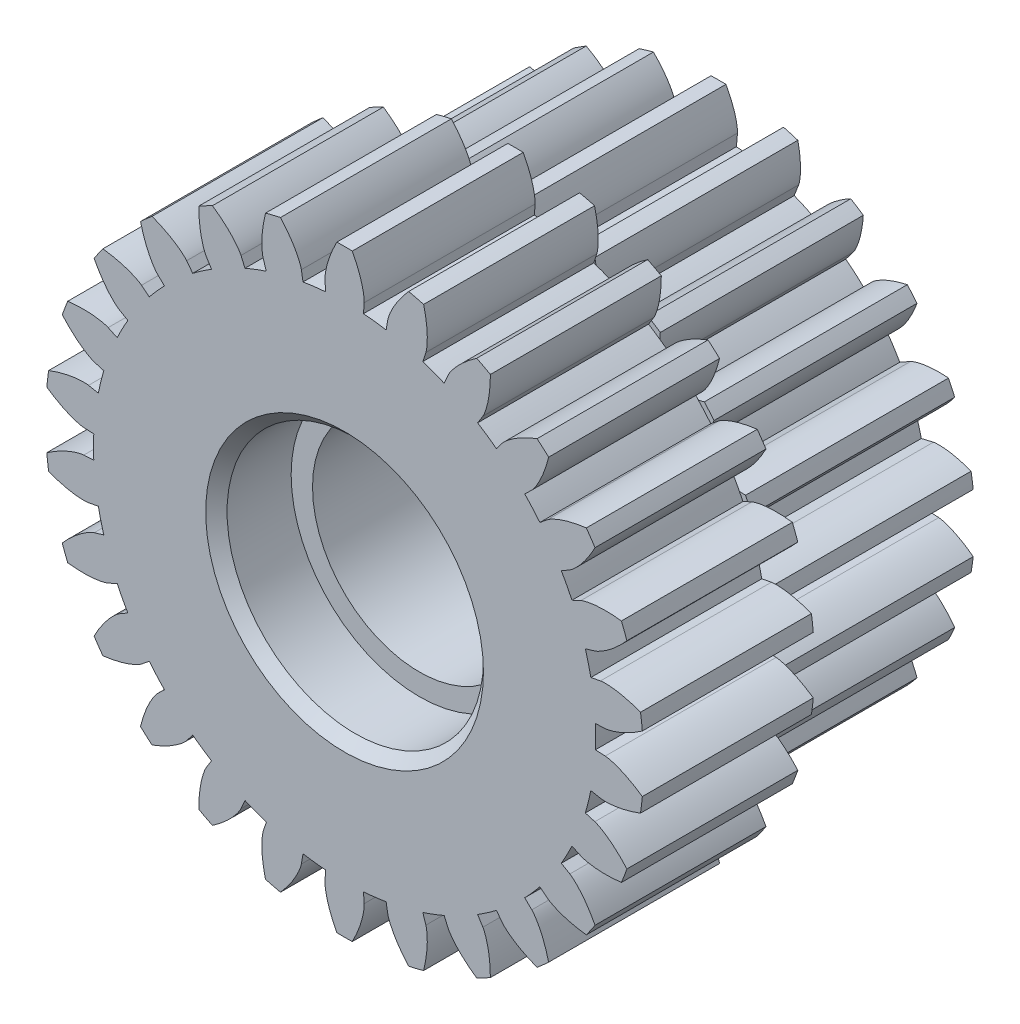
SolidWorks part; units mm, degrees
ref_plane "Front Plane" through (0, 0, 0) normal (0, 0, 1) x (1, 0, 0)
ref_plane "Top Plane" through (0, 0, 0) normal (0, 1, 0) x (1, 0, 0)
ref_plane "Right Plane" through (0, 0, 0) normal (1, 0, 0) x (0, 0, -1)
sketch "Sketch1" plane through (0, 0, 0) normal (0, 0, 1) x (1, 0, 0)
  circle A0 centre (0, 0) radius 14
  dimension "D1" = 28
extrude "Boss-Extrude1" add sketch "Sketch1" along normal mid plane 8
sketch "Sketch2" plane through (0, 0, 0) normal (0, 0, 1) x (1, 0, 0)
  line L0 (0, 0) -> (12.9865, 0.5914) construction
  line L1 (0, 0) -> (13, 0) construction
  line L2 (0, 0) -> (12.9865, -0.5914) construction
  line L3 (12.2009, -0.5557) -> (11.7378, -0.5346)
  line L4 (12.2034, 0.5558) -> (11.7378, 0.5346)
  circle A0 centre (0, 0) radius 13 construction
  circle A1 centre (0, 0) radius 12.216 construction
  circle A2 centre (0, 0) radius 11.75
  circle A3 centre (0, 0) radius 14 construction
  circle A4 centre (0, 0) radius 14
  spline S0 degree 4 poles (12.2034, 0.5558) (12.2075, 0.556) (12.2192, 0.5569) (12.2412, 0.5593) (12.2771, 0.5643) (12.3226, 0.5721) (12.3813, 0.5841) (12.45, 0.6003) (12.5252, 0.6205) (12.6066, 0.645) (12.6873, 0.6717) (12.7674, 0.7004) (12.8467, 0.7308) (12.9423, 0.7698) (13.0562, 0.8195) (13.1881, 0.882) (13.3363, 0.9581) (13.4855, 1.041) (13.631, 1.127) (13.7761, 1.219) (13.9153, 1.3115) (14.0579, 1.4127) (14.1886, 1.5087) (14.3326, 1.6219) (14.4482, 1.7148) (14.598, 1.8432) (14.6858, 1.9208) (14.7875, 2.0136) (14.8322, 2.0559) (14.8598, 2.0818) knots 0 0 0 0 0 0.005377 0.015084 0.028532 0.04661 0.064855 0.092111 0.119476 0.146842 0.174209 0.201575 0.228941 0.256307 0.307035 0.361767 0.4165 0.471232 0.525964 0.580697 0.635429 0.690161 0.744894 0.799626 0.854358 0.909091 0.954545 1 1 1 1 1 construction
  spline S1 degree 4 poles (12.2034, 0.5558) (12.2075, 0.556) (12.2192, 0.5569) (12.2412, 0.5593) (12.2771, 0.5643) (12.3226, 0.5721) (12.3813, 0.5841) (12.45, 0.6003) (12.5252, 0.6205) (12.6066, 0.645) (12.6873, 0.6717) (12.7674, 0.7004) (12.8467, 0.7308) (12.9423, 0.7698) (13.0562, 0.8195) (13.1881, 0.882) (13.3363, 0.9581) (13.4855, 1.041) (13.631, 1.127) (13.7761, 1.219) (13.9153, 1.3115) (14.0579, 1.4127) (14.1886, 1.5087) (14.3326, 1.6219) (14.4482, 1.7148) (14.5656, 1.8154) (14.6224, 1.865) (14.6513, 1.8907) knots 0 0 0 0 0 0.005377 0.015084 0.028532 0.04661 0.064855 0.092111 0.119476 0.146842 0.174209 0.201575 0.228941 0.256307 0.307035 0.361767 0.4165 0.471232 0.525964 0.580697 0.635429 0.690161 0.744894 0.799626 0.854358 0.909091 0.909091 0.909091 0.909091 0.909091
  spline S2 degree 4 poles (12.2009, -0.5557) (12.2051, -0.5559) (12.2168, -0.5568) (12.2388, -0.5592) (12.2746, -0.5642) (12.3202, -0.572) (12.3788, -0.5839) (12.4476, -0.6002) (12.5228, -0.6204) (12.6041, -0.6449) (12.6848, -0.6716) (12.7649, -0.7003) (12.8443, -0.7307) (12.9399, -0.7696) (13.0538, -0.8194) (13.1857, -0.8819) (13.3338, -0.958) (13.4831, -1.0409) (13.6285, -1.1269) (13.7737, -1.2189) (13.9129, -1.3114) (14.0555, -1.4126) (14.1861, -1.5086) (14.3301, -1.6218) (14.4457, -1.7147) (14.5956, -1.8431) (14.6833, -1.9207) (14.7851, -2.0135) (14.8298, -2.0557) (14.8573, -2.0817) knots 0 0 0 0 0 0.005377 0.015084 0.028532 0.04661 0.064855 0.092111 0.119476 0.146842 0.174209 0.201575 0.228941 0.256307 0.307035 0.361767 0.4165 0.471232 0.525964 0.580697 0.635429 0.690161 0.744894 0.799626 0.854358 0.909091 0.954545 1 1 1 1 1 construction
  spline S3 degree 4 poles (12.2009, -0.5557) (12.2051, -0.5559) (12.2168, -0.5568) (12.2388, -0.5592) (12.2746, -0.5642) (12.3202, -0.572) (12.3788, -0.5839) (12.4476, -0.6002) (12.5228, -0.6204) (12.6041, -0.6449) (12.6848, -0.6716) (12.7649, -0.7003) (12.8443, -0.7307) (12.9399, -0.7696) (13.0538, -0.8194) (13.1857, -0.8819) (13.3338, -0.958) (13.4831, -1.0409) (13.6285, -1.1269) (13.7737, -1.2189) (13.9129, -1.3114) (14.0555, -1.4126) (14.1861, -1.5086) (14.3301, -1.6218) (14.4457, -1.7147) (14.5631, -1.8153) (14.6199, -1.8649) (14.6488, -1.8905) knots 0 0 0 0 0 0.005377 0.015084 0.028532 0.04661 0.064855 0.092111 0.119476 0.146842 0.174209 0.201575 0.228941 0.256307 0.307035 0.361767 0.4165 0.471232 0.525964 0.580697 0.635429 0.690161 0.744894 0.799626 0.854358 0.909091 0.909091 0.909091 0.909091 0.909091
  dimension "D1" = 26
  dimension "D2" = 24.432
  dimension "D3" = 23.5
  dimension "D4" = 2.608
  dimension "D5" = 2.608
extrude "Cut-Extrude1" cut sketch "Sketch2" against normal through all both and the other way through all contours A2 A4 region at (13.0556, -0.0004, 0)
pattern_circular "CirPattern2" count 26 over 360 about axis through (0, 0, 4) along (0, 0, -1) of "Cut-Extrude1"
sketch "Sketch3" plane through (0, 0, 4) normal (0, 0, 1) x (1, 0, 0)
  circle A0 centre (0, 0) radius 5
  dimension "D1" = 10
sketch "Sketch4" plane through (0, 0, -4) normal (0, 0, -1) x (-1, 0, 0)
  circle A0 centre (0, 0) radius 12
  dimension "D1" = 24
extrude "Boss-Extrude2" add sketch "Sketch4" along normal blind 9.5
sketch "Sketch5" plane through (0, 0, -13.5) normal (0, 0, -1) x (-1, 0, 0)
  line L0 (0, 0) -> (12, 0) construction
  line L1 (0, 0) -> (11.9809, 0.6776) construction
  line L2 (0, 0) -> (11.9809, -0.6776) construction
  line L3 (10.3128, 0.5832) -> (9.7344, 0.5505)
  line L4 (10.3128, -0.5832) -> (9.7344, -0.5505)
  circle A0 centre (0, 0) radius 10.3366 construction
  circle A1 centre (0, 0) radius 9.75
  circle A2 centre (0, 0) radius 12
  spline S0 degree 4 poles (10.3128, 0.5832) (10.3163, 0.5835) (10.3262, 0.5844) (10.3448, 0.5866) (10.3751, 0.5911) (10.4136, 0.5982) (10.4631, 0.6088) (10.5211, 0.6232) (10.5845, 0.641) (10.6531, 0.6625) (10.7212, 0.6858) (10.7887, 0.7108) (10.8555, 0.7373) (10.9361, 0.7712) (11.032, 0.8143) (11.143, 0.8685) (11.2676, 0.9342) (11.3932, 1.0057) (11.5154, 1.0798) (11.6374, 1.159) (11.7543, 1.2386) (11.874, 1.3256) (11.9836, 1.408) (12.1045, 1.5051) (12.2014, 1.5848) (12.327, 1.6948) (12.4005, 1.7613) (12.4857, 1.8407) (12.5232, 1.8769) (12.5462, 1.8992) knots 0 0 0 0 0 0.005377 0.015084 0.028532 0.04661 0.064855 0.092111 0.119476 0.146842 0.174209 0.201575 0.228941 0.256307 0.307035 0.361767 0.4165 0.471232 0.525964 0.580697 0.635429 0.690161 0.744894 0.799626 0.854358 0.909091 0.954545 1 1 1 1 1 construction
  spline S1 degree 4 poles (10.3128, 0.5832) (10.3163, 0.5835) (10.3262, 0.5844) (10.3448, 0.5866) (10.3751, 0.5911) (10.4136, 0.5982) (10.4631, 0.6088) (10.5211, 0.6232) (10.5845, 0.641) (10.6531, 0.6625) (10.7212, 0.6858) (10.7887, 0.7108) (10.8555, 0.7373) (10.9361, 0.7712) (11.032, 0.8143) (11.143, 0.8685) (11.2676, 0.9342) (11.3932, 1.0057) (11.5154, 1.0798) (11.6374, 1.159) (11.7543, 1.2386) (11.874, 1.3256) (11.9836, 1.408) (12.1045, 1.5051) (12.2014, 1.5848) (12.2998, 1.671) (12.3474, 1.7135) (12.3716, 1.7354) knots 0 0 0 0 0 0.005377 0.015084 0.028532 0.04661 0.064855 0.092111 0.119476 0.146842 0.174209 0.201575 0.228941 0.256307 0.307035 0.361767 0.4165 0.471232 0.525964 0.580697 0.635429 0.690161 0.744894 0.799626 0.854358 0.909091 0.909091 0.909091 0.909091 0.909091
  spline S2 degree 4 poles (10.3128, -0.5832) (10.3163, -0.5835) (10.3262, -0.5844) (10.3448, -0.5866) (10.3751, -0.5911) (10.4136, -0.5982) (10.4631, -0.6088) (10.5211, -0.6232) (10.5845, -0.641) (10.6531, -0.6625) (10.7212, -0.6858) (10.7887, -0.7108) (10.8555, -0.7373) (10.9361, -0.7712) (11.032, -0.8143) (11.143, -0.8685) (11.2676, -0.9342) (11.3932, -1.0057) (11.5154, -1.0798) (11.6374, -1.159) (11.7543, -1.2386) (11.874, -1.3256) (11.9836, -1.408) (12.1045, -1.5051) (12.2014, -1.5848) (12.327, -1.6948) (12.4005, -1.7613) (12.4857, -1.8407) (12.5232, -1.8769) (12.5462, -1.8992) knots 0 0 0 0 0 0.005377 0.015084 0.028532 0.04661 0.064855 0.092111 0.119476 0.146842 0.174209 0.201575 0.228941 0.256307 0.307035 0.361767 0.4165 0.471232 0.525964 0.580697 0.635429 0.690161 0.744894 0.799626 0.854358 0.909091 0.954545 1 1 1 1 1 construction
  spline S3 degree 4 poles (10.3128, -0.5832) (10.3163, -0.5835) (10.3262, -0.5844) (10.3448, -0.5866) (10.3751, -0.5911) (10.4136, -0.5982) (10.4631, -0.6088) (10.5211, -0.6232) (10.5845, -0.641) (10.6531, -0.6625) (10.7212, -0.6858) (10.7887, -0.7108) (10.8555, -0.7373) (10.9361, -0.7712) (11.032, -0.8143) (11.143, -0.8685) (11.2676, -0.9342) (11.3932, -1.0057) (11.5154, -1.0798) (11.6374, -1.159) (11.7543, -1.2386) (11.874, -1.3256) (11.9836, -1.408) (12.1045, -1.5051) (12.2014, -1.5848) (12.2998, -1.671) (12.3474, -1.7135) (12.3716, -1.7354) knots 0 0 0 0 0 0.005377 0.015084 0.028532 0.04661 0.064855 0.092111 0.119476 0.146842 0.174209 0.201575 0.228941 0.256307 0.307035 0.361767 0.4165 0.471232 0.525964 0.580697 0.635429 0.690161 0.744894 0.799626 0.854358 0.909091 0.909091 0.909091 0.909091 0.909091
  dimension "D2" = 19.5
  dimension "D3" = 24
  dimension "D1" = 20.6732
  dimension "D4" = 3.237
  dimension "D5" = 3.237
extrude "Cut-Extrude2" cut sketch "Sketch5" against normal up to surface (9.5 mm away) contours A2 A1 region at (-11.052, 0, -13.5) up to face at (12.3272, -1.497, -4)
pattern_circular "CirPattern3" count 22 over 360 about axis through (0, 0, -13.5) along (0, 0, 1) of "Cut-Extrude2"
extrude "Cut-Extrude3" cut sketch "Sketch3" against normal through all contours A0
sketch "Sketch7" plane through (0, 0, -13.5) normal (0, 0, -1) x (-1, 0, 0)
  circle A0 centre (0, 0) radius 6
  dimension "D1" = 12
extrude "Cut-Extrude4" cut sketch "Sketch7" against normal blind 3.5
ref_plane "Plane1" through (0, 0, -4.75) normal (0, 0, -1) x (-1, 0, 0)
mirror "Mirror1" about plane through (0, 0, -4.75) normal (0, 0, -1) of "Cut-Extrude4"
chamfer "Chamfer1" distance 0.5 angle 45 2 edges at (-6, 0, 4) (-6, 0, -13.5)
equation "\"module\"= 1"
equation "\"pressure angle\"= 20deg"
equation "\"h_a\"= 1 * \"module\"'addendum"
equation "\"h_b\"= 1.25 * \"module\"'dedendum"
equation "\"clr_tip_root\"= \"h_f\" - \"h_a\"'clearance of gear tooth tip and root"
equation "\"D1@Sketch1\" = \"dp_p_b\" + 2 * \"h_a\""
equation "\"D1@Boss-Extrude1\" = \"fw_p_b\""
equation "\"D1@Sketch2\" = \"dp_p_b\""
equation "\"D2@Sketch2\"= \"db_p_b\""
equation "\"D3@Sketch2\" = \"dp_p_b\" - 2 * \"h_b\""
equation "\"Nr_s\"= \"Ns\" + \"Np_b\" + \"Np_s\"'num teeth"
equation "\"pressure_angle\"= 20deg"
equation "\"h_f\"= 1.25 * \"module\"'dedendum"
equation "\"dp_r_s\"= \"module\" * \"Nr_s\"'PCD"
equation "\"bearing_ID\"= \"module\" * ( \"Ns\" + \"Np_b\") + 6"
equation "\"bearing_OD\"= 1.18 * \"bearing_ID\" + 8.57"
equation "\"bearing_height\"= 0.09 * \"bearing_ID\" + 4.62"
equation "\"clearance_planet\"=1.5"
equation "\"case_dist\"= \"sec_carrier_thickness\" + \"clearance_planet\" + \"sun_coupler_hub_thickness\" - \"case_mounting_surface_height\""
equation "\"Motor_case_OD_max\"= \"case_mounting_PCD\" + \"case_mounting_hole_allen_socket_dia\" + \"clearance_case_mount_holes_shell_thickness\" * 2"
equation "\"case_mounting_PCD\"= \"motor_case_OD_base\" + \"case_mounting_hole_shift\" * 2"
equation "\"bearing mount thickness\"= IIF((\"bearing_OD\" + \"output_mounting_hole_dia\" * 4) > (\"Nr_s\" * \"module\" + 2 * \"h_b\"), \"output_mounting_hole_dia\" * 2, ((\"Nr_s\" * \"module\" + 2 * \"h_b\" - (\"bearing_OD\" + \"output_mounting_hole_dia\" * 4)) / 2) + \"output_mounting_hole_dia\" * 2 + \"standard_clearance_1_5mm\")"
equation "\"case_mounting_hole_dia\"=3"
equation "\"output_mounting_PCD\"= \"bearing_OD\" + \"bearing mount thickness\""
equation "\"output_mounting_hole_dia\"= 4"
equation "\"clearance_case_mount_holes_shell_thickness\"= 1"
equation "\"motor_case_OD_base\"= \"motor_OD\" + \"clearance_motor_and_case\" * 2 + \"Motor_case_thickness\" * 2"
equation "\"sec_carrier_thickness\"= 5"
equation "\"sun_coupler_hub_thickness\"= 4"
equation "\"clearance_sun_coupler_sec_carrier\"= 1.5"
equation "\"clearance_motor_and_case\"= IIF( ((\"Ns\" + \"Np_b\" * 2) * \"module\") < \"motor_OD\", 5, (((\"Ns\" + \"Np_b\" * 2) * \"module\" - \"motor_OD\") * 0.5 + 5) )"
equation "\"motor_OD\"= 72"
equation "\"Motor_case_thickness\"= 2.5"
equation "\"Motor_case_ID\"= \"motor_OD\" + \"clearance_motor_and_case\" * 2"
equation "\"case_mounting_hole_shift\"= \"case_mounting_hole_dia\" / 2 - 0.5"
equation "\"output_mounting_nut_wrench_size\"= 7"
equation "\"output_mounting_nut_thickness\"= 3.2"
equation "\"case_mounting_hole_allen_socket_dia\"= 5.5"
equation "\"output_mounting_nut_depth\"= 3"
equation "\"case_mounting_bolt_depth\"= 4.5"
equation "\"Ns\"= 20"
equation "\"ring_radial_thickness\"= 5"
equation "\"ring_to_chamfer_clearance\"= \"clearance_planet\""
equation "\"Motor_case_OD_base_to_chamfer\"=5"
equation "\"pattern_offset_from_motor_case_OD_base\"= 3"
equation "\"pattern_bulge_dia\"= 3"
equation "\"pattern_num_bulge\"= 18"
equation "\"pattern_depth\"= 2"
equation "\"motor_height\"= 27"
equation "\"case_mounting_wrench_size\"= 5.5"
equation "\"case_mounting_nut_clearance\"= 2"
equation "\"base_plate_thickness\"= 4"
equation "\"case_mounting_nut_thickness\"= 2.4"
equation "\"case_mounting_surface_height\"= 4"
equation "\"motor_mount_hole_PCD\"= 32"
equation "\"motor_mount_hole_dia\"= 4"
equation "\"motor_mount_hole_num\"= 4"
equation "\"central_hole_offset_from_motor_mount_PCD\"= 5"
equation "\"wire_slot_dist_from_center\"= 33"
equation "\"wire_slot_length\"= 10"
equation "\"wire_slot_radius\"= 4"
equation "\"driver_upper_holes_dist_from_center\"= 23"
equation "\"driver_lower_holes_dist_from_center\"= 15"
equation "\"driver_side_holes_dist_from_center\"= 20"
equation "\"driver_mount_holes_dia\"= 2.5"
equation "\"driver_mount_inserts_OD\"= 3.5"
equation "\"driver_mount_thickness\"= 1.5"
equation "\"driver_mount_height\"= 4"
equation "\"air_flow_hole_offset\"= 3"
equation "\"num_planet\"= 4"
equation "\"planet_pin_bolt_dia\"= 5"
equation "\"planet_pin_socket_head_dia\"= 8.5"
equation "\"carrier_PCD\"= ( \"Np_b\" + \"Ns\" ) * \"module\""
equation "\"planet_shaft_dia\"= 8"
equation "\"planet_shaft_step_offset\"= 1"
equation "\"carrier_trapezoidal_support_sun_offset\"= 5"
equation "\"carrier_trapezoidal_support_hole_PCD_offset_bearing_ID\"= 4"
equation "\"carrier_trapezoidal_support_hole_dia\"= 3"
equation "\"carrier_trapezoidal_support_hole_socket_head_dia\"= 5.5"
equation "\"carrier_bearing_step_width\"= 1.5"
equation "\"standard_clearance_1_5mm\"=1.5"
equation "\"standard_fillet_1_5mm\"= 1.5"
equation "\"sun_shaft_bearing_OD\"= 12"
equation "\"sun_shaft_bearing_width\"= 3.5"
equation "\"standard_bearing_insertion_chamfer\"= 0.5"
equation "\"carrier_trapezoidal_support_hole_wrench_size\"= 5.5"
equation "\"planet_pin_bolt_wrench_size\"= 8"
equation "\"planet_bearing_OD\"= 12"
equation "\"planet_bearing_width\"= 3.5"
equation "\"planet_bore\"= 10"
equation "\"D1@Sketch3\"=\"planet_bore\""
equation "\"Np_b\"= 26"
equation "\"dp_s\"= \"module\" * \"Ns\"'PCD"
equation "\"db_s\"= \"dp_s\" * cos ( \"pressure angle\" )'base CD"
equation "\"fw_s_calc\"= 10mm'face width"
equation "\"alpha_s\"= sqr ( \"dp_s\" ^ 2 - \"db_s\" ^ 2 ) / \"db_s\" * 180 / pi - \"pressure angle\""
equation "\"beta_s\"= ( 360 / ( 4 * \"Ns\" ) - \"alpha_s\" ) * 2"
equation "\"dp_p_b\"= \"module\" * \"Np_b\"'PCD"
equation "\"db_p_b\"= \"dp_p_b\" * cos ( \"pressure angle\" )'base CD"
equation "\"fw_p_s\"= \"fw_r_s\" + \"clearance_planet\""
equation "\"alpha_p_b\"= sqr ( \"dp_p_b\" ^ 2 - \"db_p_b\" ^ 2 ) / \"db_p_b\" * 180 / pi - \"pressure angle\""
equation "\"beta_p_b\"= ( 360 / ( 4 * \"Np_b\" ) - \"alpha_p_b\" ) * 2"
equation "\"motor_output_hole_PCD\"= 22"
equation "\"motor_output_hole_dia\"= 3"
equation "\"motor_output_hole_num\"= 4"
equation "\"sun_shaft_bearing_ID\"= 8"
equation "\"sun_hub_dia\"= \"motor_output_hole_PCD\" + \"motor_output_hole_dia\" + \"standard_clearance_1_5mm\" * 2"
equation "\"sun_central_bolt_dia\"= 5"
equation "\"sun_central_bolt_socket_head_dia\"= 8.5"
equation "\"fw_s_used\"= \"fw_p_s\" + \"fw_p_b\" + \"clearance_planet\" + \"sec_carrier_thickness\" + \"standard_clearance_1_5mm\" - \"carrier_small_ring_inner_bearing_flap\" +  \"standard_clearance_1_5mm\" "
equation "\"motor_output_hole_CSK_OD\"= 9'8.96 is exact value"
equation "\"motor_output_hole_CSK_head_height\"= 2.5"
equation "\"bearing_retainer_thickness\"= 2"
equation "\"Np_s\"= 22"
equation "\"fw_p_b\"= 8"
equation "\"dp_p_s\"= \"module\" * \"Np_s\"'PCD"
equation "\"db_p_s\"= \"dp_p_s\" * cos ( \"pressure angle\" )'base CD"
equation "\"alpha_p_s\"= sqr ( \"dp_p_s\" ^ 2 - \"db_p_s\" ^ 2 ) / \"db_p_s\" * 180 / pi - \"pressure angle\""
equation "\"beta_p_s\"= ( 360 / ( 4 * \"Np_s\" ) - \"alpha_p_s\" ) * 2"
equation "\"D1@Sketch4\"=\"dp_p_s\" + 2 * \"h_a\""
equation "\"D1@Boss-Extrude2\"=\"fw_p_s\""
equation "\"D2@Sketch5\"=\"dp_p_s\" - 2 * \"h_b\""
equation "\"D3@Sketch5\"=\"dp_p_s\"+2 * \"h_a\" "
equation "\"D1@Sketch5\"=\"db_p_s\""
equation "\"D1@CirPattern3\"=\"Np_s\""
equation "\"D4@Sketch5\"=\"beta_p_s\"/2"
equation "\"D5@Sketch5\"=\"beta_p_s\"/2"
equation "\"D4@Sketch2\"=\"beta_p_b\"/2"
equation "\"D5@Sketch2\"=\"beta_p_b\"/2"
equation "\"D1@Sketch7\"=\"planet_bearing_OD\""
equation "\"D1@Cut-Extrude4\"=\"planet_bearing_width\""
equation "\"D1@Chamfer1\"=\"standard_bearing_insertion_chamfer\""
equation "\"D1@CirPattern2\"=\"Np_b\""
equation "\"Nr_b\"= \"Ns\" + \"Np_b\" * 2"
equation "\"dp_r_b\"= \"module\" * \"Nr_b\"'PCD"
equation "\"db_r_b\"= \"dp_r_b\" * cos ( \"pressure_angle\" )'base CD"
equation "\"fw_r_b\"= \"fw_p_b\"'face width"
equation "\"alpha_r_b\"= sqr ( \"dp_r_b\" ^ 2 - \"db_r_b\" ^ 2 ) / \"db_r_b\" * 180 / pi - \"pressure_angle\""
equation "\"beta_r_b\"= ( 360 / ( 4 * \"Nr_b\" ) + \"alpha_r_b\" ) * 2"
equation "\"ring_OD_b\"= \"Nr_b\" * \"module\" + \"ring_radial_thickness\" * 2"
equation "\"Fillet10\"= IIF ( \"ring_OD_b\" > ( \"bearing_OD\" + 2 * \"bearing mount thickness\" ) , \"suppressed\" , \"unsuppressed\" )"
equation "\"Fillet11\"= IIF ( \"ring_OD_b\" < ( \"bearing_OD\" + 2 * \"bearing mount thickness\" ) , \"suppressed\" , \"unsuppressed\" )"
equation "\"clr_tip_root_s\"= \"h_f\" - \"h_a\"'clearance of gear tooth tip and root"
equation "\"db_r_s\"= \"dp_r_s\" * cos ( \"pressure_angle\" )'base CD"
equation "\"fw_r_s\"= 8mm'face width"
equation "\"alpha_r_s\"= sqr ( \"dp_r_s\" ^ 2 - \"db_r_s\" ^ 2 ) / \"db_r_s\" * 180 / pi - \"pressure_angle\""
equation "\"beta_r_s\"= ( 360 / ( 4 * \"Nr_s\" ) + \"alpha_r_s\" ) * 2"
equation "\"small_ring_case_thickness\"= 4mm"
equation "\"carrier_thickness\"= 4mm"
equation "\"small_ring_output_wall_thickness\"= 5mm"
equation "\"small_ring_output_wall_to_bearing_shaft_attachement_hole_dia\"= 4mm"
equation "\"small_ring_output_wall_to_bearing_shaft_attachement_hole_depth\"= 6.5mm"
equation "\"small_ring_output_wall_to_bearing_shaft_attachement_nut_wrench\"= 7mm"
equation "\"small_ring_output_wall_to_bearing_shaft_attachement_nut_thickness\"= 3.2mm"
equation "\"small_ring_output_wall_to_bearing_shaft_attachement_hole_pcd\"= 12mm"
equation "\"small_ring_output_wall_to_bearing_shaft_attachement_hole_num\"= 3"
equation "\"small_ring_output_wall_to_bearing_shaft_attachement_hole_CSK_OD\"= 9mm"
equation "\"small_ring_output_wall_to_bearing_shaft_attachement_hole_CSK_head_height\"= 2.5mm"
equation "\"carrier_small_ring_inner_bearing_ID\"= 20mm"
equation "\"carrier_small_ring_inner_bearing_OD\"= 32mm"
equation "\"carrier_small_ring_inner_bearing_height\"= 7mm"
equation "\"carrier_small_ring_inner_bearing_flap\"= 2mm"
equation "\"gear_casing_big_ring_to_bearing_dist\"=\"fw_p_s\" + \"clearance_planet\" + \"carrier_thickness\" + \"standard_clearance_1_5mm\"*2/3 + \"small_ring_case_thickness\" "
equation "\"gear_casing_thickness\"= 4"
